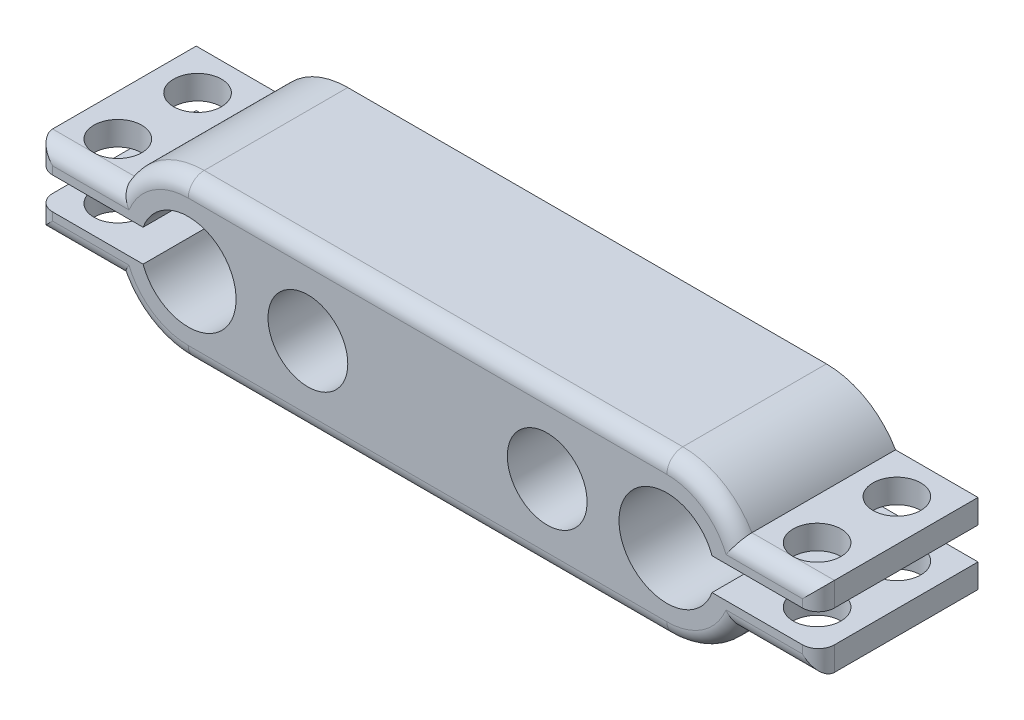
SolidWorks part; units mm, degrees
ref_plane "정면" through (0, 0, 0) normal (0, 0, 1) x (1, 0, 0)
ref_plane "윗면" through (0, 0, 0) normal (0, 1, 0) x (1, 0, 0)
ref_plane "우측면" through (0, 0, 0) normal (1, 0, 0) x (0, 0, -1)
sketch "스케치1" plane through (0, 0, 0) normal (0, 0, 1) x (1, 0, 0)
  line L0 (0, 11.8481) -> (0, 0) construction
  line L1 (15, 0) -> (-15, 0) construction
  line L2 (-22.5, 0) -> (-7.5, 0) construction
  line L3 (-24.5, -6) -> (24.5, -6)
  line L4 (-24.5, -6) -> (-24.5, 6)
  line L5 (-24.5, 6) -> (24.5, 6)
  line L6 (24.5, -6) -> (24.5, 6)
  line L7 (-24.5, -6) -> (24.5, 6) construction
  line L8 (-24.5, 6) -> (24.5, -6) construction
  line L9 (22.5, 0) -> (7.5, 0) construction
  circle A0 centre (-15, 0) radius 3
  circle A1 centre (15, 0) radius 3
  circle A4 centre (-7.5, 0) radius 2.5
  circle A5 centre (7.5, 0) radius 2.5
  dimension "D2" = 6
  dimension "D5" = 5
  dimension "D1" = 30
  dimension "D3" = 49
  dimension "D4" = 12
  dimension "D6" = 7.5
extrude "보스-돌출1" add sketch "스케치1" along normal blind 10
sketch "스케치2" plane through (0, 0, 10) normal (0, 0, 1) x (1, 0, 0)
  line L0 (-15, 0) -> (15, 0) construction
  line L1 (-15, 5) -> (15, 5)
  line L2 (-15, -5) -> (15, -5)
  line L3 (-24.5, 6) -> (-24.5, -6) construction
  line L4 (-24.5, 2.5) -> (-16.5, 2.5)
  line L5 (-24.5, 2.5) -> (-24.5, 1)
  line L6 (-24.5, 1) -> (-16.5, 1)
  line L7 (-16.5, 2.5) -> (-16.5, 1)
  line L8 (-24.5, -2.5) -> (-24.5, -1)
  line L9 (-24.5, -2.5) -> (-16.5, -2.5)
  line L10 (-16.5, -2.5) -> (-16.5, -1)
  line L11 (-24.5, -1) -> (-16.5, -1)
  line L12 (0, -5) -> (0, 5) construction
  line L13 (24.5, -2.5) -> (16.5, -2.5)
  line L14 (24.5, -1) -> (16.5, -1)
  line L15 (16.5, -2.5) -> (16.5, -1)
  line L16 (16.5, 2.5) -> (16.5, 1)
  line L17 (24.5, 1) -> (16.5, 1)
  line L18 (24.5, 2.5) -> (24.5, 1)
  line L19 (24.5, 2.5) -> (16.5, 2.5)
  arc A0 (-15, 5) -> (-15, -5) centre (-15, 0) ccw
  arc A1 (15, -5) -> (15, 5) centre (15, 0) ccw
  circle A2 centre (-15, 0) radius 3 construction
  circle A3 centre (-15, 0) radius 3
  point P4 (0, 0)
  point P24 (0, 0)
  circle M2 centre (-15, 0) radius 3
  line M3 (24.5, -6) -> (24.5, 6)
  line M4 (24.5, 6) -> (-24.5, 6)
  line M5 (-24.5, 6) -> (-24.5, -6)
  line M6 (-24.5, -6) -> (24.5, -6)
  circle M7 centre (15, 0) radius 3
  dimension "D1" = 2
  dimension "D2" = 1.5
  dimension "D3" = 8
  dimension "D4" = 1
extrude "컷-돌출1" cut sketch "스케치2" against normal through all contours A1 L19 L4 A0 L1 M3 M4 M5 | A1 L2 A0 L9 L13 M5 M6 M3 | A0 L6 L11 M5 | A1 L14 L17 M3 | L6 A0 L11 M2 | L14 A1 L17 M7 region at (-17.7456, 4.7556, 10) region at (-22.2331, 0, 10) region at (-18.9546, 0, 10) region at (18.9546, 0, 10) region at (22.2331, 0, 10) region at (-17.7456, -4.7556, 10)
sketch "스케치3" plane through (0, 5, 0) normal (0, 1, 0) x (1, 0, 0)
  line L0 (19.3301, -10) -> (24.5, -10) construction
  line L1 (24.5, -10) -> (24.5, 0) construction
  line L2 (24.5, 0) -> (19.3301, 0) construction
  line L3 (19.3301, 0) -> (19.3301, -10) construction
  line L4 (-24.5, -10) -> (-19.3301, -10) construction
  line L5 (-19.3301, -10) -> (-19.3301, 0) construction
  line L6 (-19.3301, 0) -> (-24.5, 0) construction
  line L7 (-24.5, 0) -> (-24.5, -10) construction
  line L8 (19.3301, -10) -> (24.5, -10)
  line L9 (24.5, -10) -> (24.5, 0)
  line L10 (24.5, 0) -> (19.3301, 0)
  line L11 (19.3301, 0) -> (19.3301, -10)
  line L12 (-24.5, -10) -> (-19.3301, -10)
  line L13 (-19.3301, -10) -> (-19.3301, 0)
  line L14 (-19.3301, 0) -> (-24.5, 0)
  line L15 (-24.5, 0) -> (-24.5, -10)
  line L16 (-21.9151, 0) -> (-21.9151, -10) construction
  line L17 (-24.5, -5) -> (-19.3301, -5) construction
  line L18 (0, 0) -> (0, -10) construction
  line L19 (-15, 0) -> (15, 0) construction
  line L20 (-15, -10) -> (15, -10) construction
  line L21 (24.5, -5) -> (19.3301, -5) construction
  line L22 (21.9151, 0) -> (21.9151, -10) construction
  line L23 (24.5, 0) -> (24.5, -10)
  line L24 (19.3301, 0) -> (24.5, 0)
  line L25 (19.3301, -10) -> (19.3301, 0)
  line L26 (24.5, -10) -> (19.3301, -10)
  circle A0 centre (-21.9151, -2.5) radius 1.5
  circle A1 centre (-21.9151, -7.5) radius 1.5
  circle A2 centre (21.9151, -7.5) radius 1.5
  circle A3 centre (21.9151, -2.5) radius 1.5
  dimension "D2" = 3
  dimension "D1" = 5
extrude "컷-돌출2" cut sketch "스케치3" against normal through all contours A0 | A1 | A3 | A2
fillet "필렛1" radius 1 14 edges at (17.5, -4.3301, 10) (0, -5, 10) (-17.5, 4.3301, 10) (0, 5, 10) (-24.5, -1.75, 10) (-24.5, 1.75, 10) (24.5, -1.75, 10) (24.5, 1.75, 10) (21.9151, -2.5, 10) (-17.5, -4.3301, 10) (-21.9151, -2.5, 10) (-21.9151, 2.5, 10) (17.5, 4.3301, 10) (21.9151, 2.5, 10)
